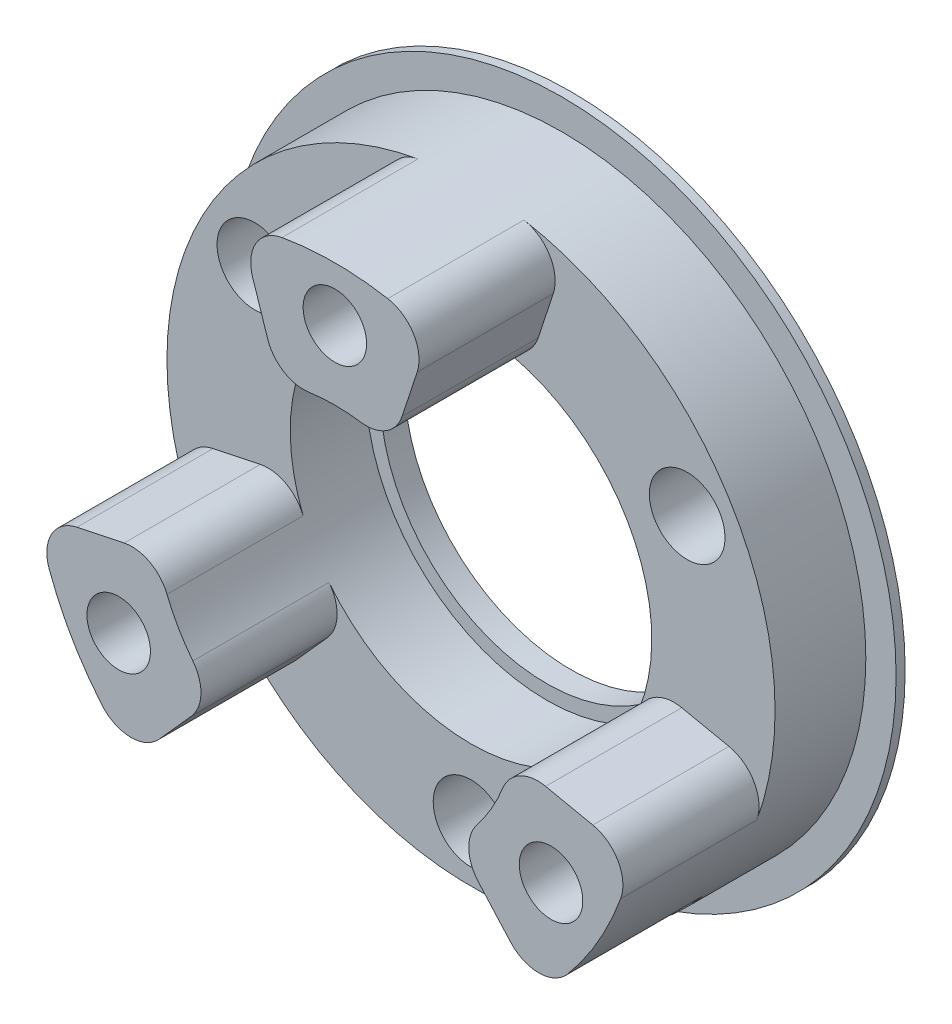
SolidWorks part; units mm, degrees
ref_plane "Front Plane" through (0, 0, 0) normal (0, 0, 1) x (1, 0, 0)
ref_plane "Top Plane" through (0, 0, 0) normal (0, 1, 0) x (1, 0, 0)
ref_plane "Right Plane" through (0, 0, 0) normal (1, 0, 0) x (0, 0, -1)
sketch "Sketch1" plane through (0, 0, 0) normal (0, 0, 1) x (1, 0, 0)
  circle A0 centre (0, 0) radius 11.95
  circle A1 centre (0, 0) radius 11
  circle A2 centre (0, 0) radius 20.1
  circle A3 centre (0, 0) radius 16.5 construction
  circle A4 centre (0, 16.5) radius 2.1
  circle A5 centre (14.2894, -8.25) radius 2.1
  circle A6 centre (-14.2894, -8.25) radius 2.1
  circle A7 centre (0, -16.5) radius 2.5
  circle A8 centre (-14.2894, 8.25) radius 2.5
  circle A9 centre (14.2894, 8.25) radius 2.5
  point P14 (0, 0)
  point P21 (0, 0)
  dimension "D1" = 23.9
  dimension "D2" = 22
  dimension "D3" = 40.2
  dimension "D4" = 33
  dimension "D5" = 4.2
  dimension "D7" = 5
  dimension "D6" = 3
  dimension "D8" = 3
extrude "Boss-Extrude1" add sketch "Sketch1" along normal blind 14.5 contours A2 A9 A8 A7 A6 A5 A4 A0 region at (-19.5315, 0, 0)
extrude "Boss-Extrude2" add sketch "Sketch1<3>" against normal blind 1 from offset 0.5 contours A0 A1 | A2 A9 A8 A7 A6 A5 A4 A0 region at (-11.612, 0, 0) region at (-19.5315, 0, 0)
sketch "Sketch1<3>" plane through (0, 0, 0) normal (0, 0, 1) x (1, 0, 0) same geometry as "Sketch1"
sketch "Sketch2" plane through (0, 0, 0) normal (0, 0, 1) x (-1, 0, 0)
  line L0 (-7.7516, 1.6208) -> (-19.6745, 4.1139)
  line L1 (0, 7.9192) -> (0, 26.8969) construction
  line L2 (7.7516, 1.6208) -> (19.6745, 4.1139)
  line L3 (19.6745, 4.1139) -> (23.7892, 4.9743) construction
  line L4 (-19.6745, 4.1139) -> (-23.7892, 4.9743) construction
  line L5 (0, 0) -> (-7.7516, 1.6208) construction
  line L6 (0, 0) -> (0, 7.9192) construction
  line L7 (0, 0) -> (7.7516, 1.6208) construction
  line L8 (0, 0) -> (-9.0322, -27.4884)
  line L9 (0, 0) -> (9.0322, -27.4884)
  circle A0 centre (0, 0) radius 11 construction
  circle A1 centre (-14.2894, -8.25) radius 2.5
  arc A2 (-9.0742, -17.9351) -> (-12.038, 2.5171) centre (-14.2894, -8.25) ccw construction
  circle A3 centre (-14.2894, -8.25) radius 2.5 construction
  circle A4 centre (0, 0) radius 20.1 construction
  arc A5 (7.7516, 1.6208) -> (-7.7516, 1.6208) centre (0, 0) ccw
  arc A6 (19.6745, 4.1139) -> (-19.6745, 4.1139) centre (0, 0) ccw
  arc A7 (-3.3416, -7.1797) -> (7.7516, 1.6208) centre (0, 0) ccw
  arc A8 (-9.0742, -17.9351) -> (19.6745, 4.1139) centre (0, 0) ccw
  arc A9 (-7.8886, 0.6959) -> (-3.3416, -7.1797) centre (0, 0) ccw
  arc A10 (-7.7516, 1.6208) -> (-7.8886, 0.6959) centre (0, 0) ccw
  arc A11 (-12.038, 2.5171) -> (-20.0694, 1.1091) centre (-14.2894, -8.25) ccw construction
  arc A12 (-19.6745, 4.1139) -> (-20.0694, 1.1091) centre (0, 0) ccw
  arc A13 (-20.0694, 1.1091) -> (-9.0742, -17.9351) centre (0, 0) ccw
  arc A14 (-20.0694, 1.1091) -> (-9.0742, -17.9351) centre (-14.2894, -8.25) ccw construction
  dimension "D1" = 22
extrude "Cut-Extrude2" cut sketch "Sketch2" against normal blind 9 from surface contours A12 A13 A8 L8 A7 A9 A10 L0 A1 region at (11.5679, 6.6787, 0) starting at face at (16.7894, 8.25, 14.5)
pattern_circular "CirPattern2" count 3 over 360 about axis through (0, 0, 14.5) along (0, 0, -1) of "Cut-Extrude2" reverse direction yes
fillet "Fillet1" radius 2.5 12 edges at (6.2745, 19.0956, 10) (-3.7304, 11.3528, 10) (-6.2745, 19.0956, 10) (3.7304, 11.3528, 10) (7.9667, -8.907, 10) (11.697, -2.4458, 10) (19.6745, -4.1139, 10) (13.4, -14.9817, 10) (-7.9667, -8.907, 10) (-13.4, -14.9817, 10) (-19.6745, -4.1139, 10) (-11.697, -2.4458, 10)
sketch "Sketch4" plane through (0, 0, -0.5) normal (0, 0, -1) x (-1, 0, 0)
  circle A0 centre (0, -16.5) radius 2.5 construction
  circle A1 centre (0, 0) radius 20.1
  circle A2 centre (0, 0) radius 20.1
  circle A3 centre (14.2894, 8.25) radius 2.5 construction
  circle A4 centre (-14.2894, 8.25) radius 2.5 construction
  circle A5 centre (0, -16.5) radius 2.5
  circle A6 centre (14.2894, 8.25) radius 2.5
  circle A7 centre (-14.2894, 8.25) radius 2.5
  circle M4 centre (-14.2894, 8.25) radius 2.5
  circle M5 centre (14.2894, 8.25) radius 2.5
  circle M6 centre (0, -16.5) radius 2.5
  dimension "D1" = 0
extrude "Boss-Extrude3" add sketch "Sketch4" against normal blind 2 contours M4 | M5 | M6 region at (0, -16.5, -0.5) region at (-14.2894, 8.25, -0.5) region at (14.2894, 8.25, -0.5)
sketch "Sketch5" plane through (0, 0, -0.5) normal (0, 0, -1) x (-1, 0, 0)
  circle A0 centre (0, 0) radius 11
  circle A1 centre (0, 0) radius 22.1
  circle A2 centre (14.2894, -8.25) radius 2.1 construction
  circle A3 centre (-14.2894, -8.25) radius 2.1 construction
  circle A4 centre (0, 16.5) radius 2.1 construction
  circle A5 centre (14.2894, -8.25) radius 2.1
  circle A6 centre (-14.2894, -8.25) radius 2.1
  circle A7 centre (0, 16.5) radius 2.1
  dimension "D1" = 44.2
extrude "Boss-Extrude4" add sketch "Sketch5" along normal blind 0.6
